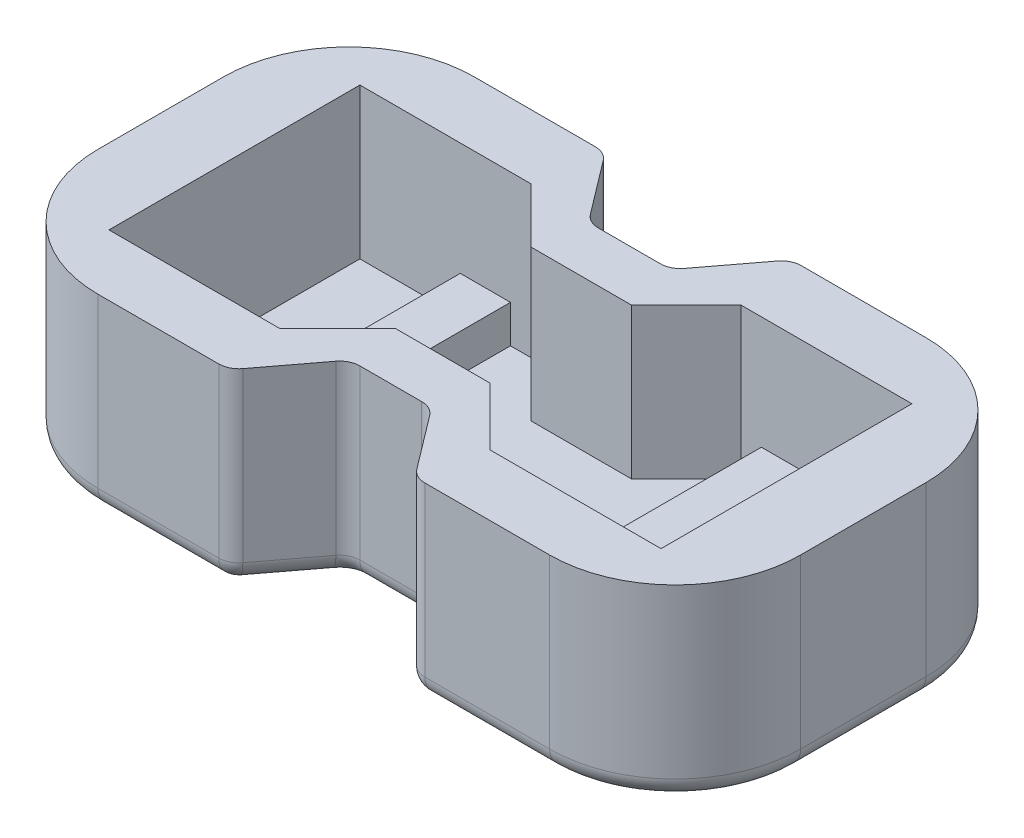
SolidWorks part; units mm, degrees
ref_plane "Front Plane" through (0, 0, 0) normal (0, 0, 1) x (1, 0, 0)
ref_plane "Top Plane" through (0, 0, 0) normal (0, 1, 0) x (1, 0, 0)
ref_plane "Right Plane" through (0, 0, 0) normal (1, 0, 0) x (0, 0, -1)
sketch "Sketch1" plane through (0, 0, 0) normal (0, 1, 0) x (1, 0, 0)
  line L1 (-35.56, 19.05) -> (35.56, 19.05)
  line L2 (-35.56, 19.05) -> (-35.56, -19.05)
  line L3 (-35.56, -19.05) -> (35.56, -19.05)
  line L4 (35.56, 19.05) -> (35.56, -19.05)
  line L5 (-35.56, 19.05) -> (35.56, -19.05) construction
  line L6 (-35.56, -19.05) -> (35.56, 19.05) construction
  point P0 (0, 0)
  dimension "D1" = 38.1
  dimension "D2" = 71.12
extrude "Boss-Extrude1" add sketch "Sketch1" along normal blind 3.81
sketch "Sketch2" plane through (0, 3.81, 0) normal (0, 1, 0) x (1, 0, 0)
  line L0 (-5.08, 7) -> (-10.6242, 12.5442)
  line L1 (-5.08, 7) -> (5.08, 7)
  line L2 (27.94, -7) -> (27.94, 7)
  line L3 (-4.7684, -7) -> (4.7684, -7)
  line L4 (-27.94, -7) -> (-27.94, 7)
  line L5 (27.94, -7) -> (-27.94, 7) construction
  line L6 (27.94, 7) -> (-27.94, -7) construction
  line L7 (-10.6242, 12.5442) -> (-27.94, 12.5442)
  line L8 (-27.94, 12.5442) -> (-27.94, -12.8558)
  line L9 (-27.94, -12.8558) -> (-10.6242, -12.8558)
  line L10 (-10.6242, -12.8558) -> (-4.7684, -7)
  line L11 (0, 31.6155) -> (0, -38.8322) construction
  line L12 (27.94, 12.5442) -> (27.94, -12.8558)
  line L13 (27.94, -12.8558) -> (10.6242, -12.8558)
  line L14 (10.6242, -12.8558) -> (4.7684, -7)
  line L15 (5.08, 7) -> (10.6242, 12.5442)
  line L16 (10.6242, 12.5442) -> (27.94, 12.5442)
  point P0 (0, 0)
  line M8 (35.56, -19.05) -> (35.56, 19.05)
  line M9 (35.56, 19.05) -> (-35.56, 19.05)
  line M10 (-35.56, 19.05) -> (-35.56, -19.05)
  line M11 (-35.56, -19.05) -> (35.56, -19.05)
  dimension "D1" = 55.88
  dimension "D2" = 14
  dimension "D3" = 25.4
  dimension "D4" = 22.86
extrude "Boss-Extrude2" add sketch "Sketch2" along normal blind 15.24 contours L15 L16 L12 L2 L13 L14 L3 L10 L9 L8 L4 L7 L0 L1 M11 M8 M9 M10 region at (0, 3.81, 18.2432)
sketch "Sketch3" plane through (0, 3.81, 0) normal (0, 1, 0) x (1, 0, 0)
  line L4 (-17.78, -14.1662) -> (-12.7, -14.1662)
  line L5 (-17.78, -14.1662) -> (-17.78, 14.1662)
  line L6 (-17.78, 14.1662) -> (-12.7, 14.1662)
  line L7 (-12.7, -14.1662) -> (-12.7, 14.1662)
  line L9 (-17.78, -14.1662) -> (-12.7, 14.1662) construction
  line L10 (-17.78, 14.1662) -> (-12.7, -14.1662) construction
  line L18 (12.7, -15.4758) -> (17.78, -15.4758)
  line L19 (12.7, -15.4758) -> (12.7, 15.4758)
  line L20 (12.7, 15.4758) -> (17.78, 15.4758)
  line L21 (17.78, -15.4758) -> (17.78, 15.4758)
  line L22 (12.7, -15.4758) -> (17.78, 15.4758) construction
  line L23 (12.7, 15.4758) -> (17.78, -15.4758) construction
  point P0 (-15.24, 0)
  point P6 (0, 0)
  point P10 (0, 0)
  point P12 (15.24, 0)
  dimension "D1" = 5.08
  dimension "D2" = 5.08
extrude "Boss-Extrude3" add sketch "Sketch3" along normal blind 3.81
extrude "Boss-Extrude4" add sketch "Sketch3<2>" along normal blind 3.81
sketch "Sketch3<2>" plane through (0, 3.81, 0) normal (0, 1, 0) x (1, 0, 0) same geometry as "Sketch3"
fillet "Fillet1" radius 12.7 1 edges at (35.56, 9.525, 19.05)
fillet "Fillet2" radius 12.7 1 edges at (35.56, 9.525, -19.05)
fillet "Fillet3" radius 12.7 2 edges at (-35.56, 9.525, -19.05) (-35.56, 9.525, 19.05)
fillet "Fillet4" radius 2.032 8 edges at (-31.8403, 0, 15.3303) (-35.56, 0, 0) (-31.8403, 0, -15.3303) (0, 0, -19.05) (31.8403, 0, -15.3303) (35.56, 0, 0) (31.8403, 0, 15.3303) (0, 0, 19.05)
sketch "Sketch4" plane through (0, 19.05, 0) normal (0, 1, 0) x (1, 0, 0)
  line L0 (-9.6184, -19.05) -> (-4.3395, -12.08)
  line L1 (-22.86, -19.05) -> (22.86, -19.05) construction
  line L2 (-4.3395, -12.08) -> (3.9437, -12.08)
  line L3 (3.9437, -12.08) -> (9.2227, -19.05)
  line L4 (-4.7684, -7) -> (4.7684, -7) construction
  line L5 (-23.2698, 0) -> (40.3002, 0) construction
  line L6 (-9.6184, -19.05) -> (9.2227, -19.05)
  dimension "D1" = 5.08
  dimension "D2" = 127.139
  dimension "D3" = 127.14
extrude "Cut-Extrude5" cut sketch "Sketch4" against normal through all
mirror "Mirror1" about plane through (0, 0, 0) normal (0, 0, 1) of "Cut-Extrude5"
fillet "Fillet5" radius 2.032 18 edges at (9.2227, 10.541, -19.05) (9.2227, 10.541, 19.05) (8.7719, 0.5952, -18.4548) (8.7719, 0.5952, 18.4548) (5.8137, 0, -14.549) (5.8137, 0, 14.549) (-0.1979, 0, -12.08) (-0.1979, 0, 12.08) (-6.2095, 0, -14.549) (-9.1676, 0.5952, -18.4548) (-6.2095, 0, 14.549) (-9.1676, 0.5952, 18.4548) (3.9437, 9.525, -12.08) (-4.3395, 9.525, -12.08) (-9.6184, 10.541, -19.05) (3.9437, 9.525, 12.08) (-4.3395, 9.525, 12.08) (-9.6184, 10.541, 19.05)
